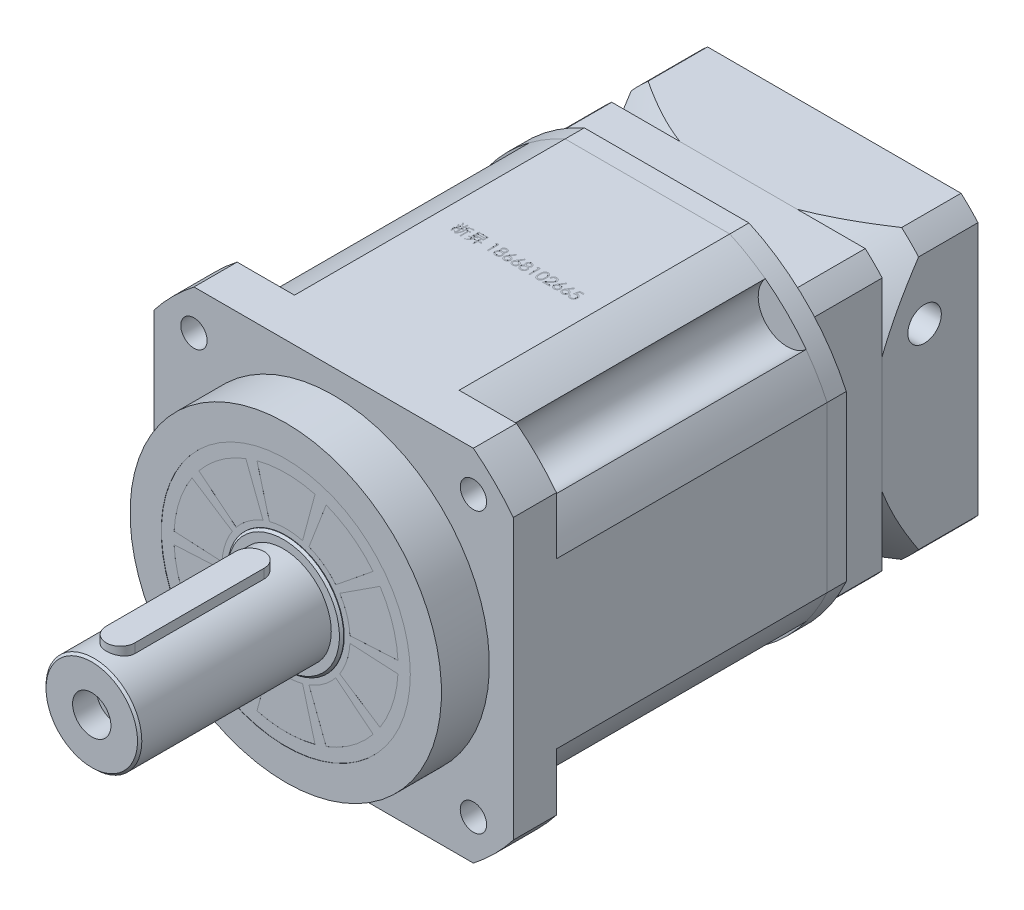
SolidWorks part; units mm, degrees
ref_plane "前视基准面" through (0, 0, 0) normal (0, 0, 1) x (1, 0, 0)
ref_plane "上视基准面" through (0, 0, 0) normal (0, 1, 0) x (1, 0, 0)
ref_plane "右视基准面" through (0, 0, 0) normal (1, 0, 0) x (0, 0, -1)
sketch "草图1" plane through (0, 0, 0) normal (1, 0, 0) x (0, 0, -1)
  line L0 (-155, 0) -> (155, 0) construction
  line L1 (155, 0) -> (155, 75)
  line L2 (155, 75) -> (-54, 75)
  line L3 (-54, 75) -> (-54, 65)
  line L4 (-54, 65) -> (-74, 65)
  line L5 (-74, 65) -> (-74, 24.3)
  line L6 (-74, 24.3) -> (-75, 24.3)
  line L7 (-75, 24.3) -> (-75, 20)
  line L8 (-75, 20) -> (-155, 20)
  line L9 (-155, 20) -> (-155, 0)
  line L10 (155, 55) -> (145, 55)
  line L11 (145, 55) -> (145, 11)
  line L12 (145, 11) -> (95.5, 11)
  line L13 (95.5, 11) -> (95.5, 0)
  line L14 (155, 44) -> (110.375, 44)
  line L15 (110.375, 44) -> (110.375, 0)
  line L16 (132.6875, 44) -> (132.6875, 0) construction
  line L17 (155, 44) -> (145, 11) construction
  line L18 (150, 27.5) -> (110.375, 27.5) construction
  point P3 (-36, 75)
  point P12 (-149, 20)
  point P13 (-83, 20)
  point P14 (95.5, 0)
  point P15 (145, 0)
  point P18 (85, 75)
  point P22 (115, 75)
  point P30 (132.6875, 27.5)
  point P31 (132.6875, -27.5)
  point P32 (-75, 0)
  point P33 (5, 0)
  point P34 (-5, 0)
  point P35 (145, 0)
  point P36 (105, 0)
  point P37 (77, 75)
  dimension "D1" = 150
  dimension "A" = 310
  dimension "D2" = 18
  dimension "D3" = 20
  dimension "D4" = 80
  dimension "D5" = 66
  dimension "D6" = 6
  dimension "D7" = 40
  dimension "D8" = 48.6
  dimension "D9" = 130
  dimension "D10" = 101
  dimension "D11" = 50
  dimension "C" = 59.5
  dimension "D12" = 10
  dimension "D13" = 110
  dimension "D14" = 22
  dimension "D15" = 70
  dimension "D16" = 40
  dimension "D17" = 44.625
  dimension "D18" = 88
  dimension "D19" = 21
  dimension "D20" = 80
  dimension "D21" = 10
  dimension "D22" = 10
  dimension "D23" = 8
sketch "草图2" plane through (0, 0, 0) normal (0, 0, 1) x (1, 0, 0)
  line L0 (0, 0) -> (0, 75) construction
  line L1 (-75, 75) -> (75, 75)
  line L2 (-75, 75) -> (-75, -75)
  line L3 (-75, -75) -> (75, -75)
  line L4 (75, 75) -> (75, -75)
  line L5 (0, 0) -> (75, 0) construction
  line L6 (-6, 23) -> (6, 23)
  line L7 (6, 23) -> (6, 19.0788)
  line L8 (-6, 23) -> (-6, 19.0788)
  line L9 (0, 0) -> (58.3363, 58.3363) construction
  line L10 (0, 0) -> (-51.2652, 51.2652) construction
  line L12 (-60, 60) -> (60, 60)
  line L13 (-60, 60) -> (-60, -60)
  line L14 (-60, -60) -> (60, -60)
  line L15 (60, 60) -> (60, -60)
  circle A0 centre (0, 0) radius 20
  circle A1 centre (0, 0) radius 8
  circle A2 centre (0, 0) radius 82.5 construction
  circle A3 centre (58.3363, 58.3363) radius 5.5
  circle A4 centre (0, 0) radius 95
  circle A5 centre (-51.2652, 51.2652) radius 4
  circle A7 centre (58.3363, 58.3363) radius 12.1
  circle A8 centre (0, 0) radius 72.5 construction
  point P13 (0, -20)
  dimension "D2" = 12
  dimension "D4" = 16
  dimension "D5" = 165
  dimension "D7" = 11
  dimension "D8" = 190
  dimension "D9" = 8
  dimension "D11" = 24.2
  dimension "D12" = 145
  dimension "D1" = 150
  dimension "D3" = 43
  dimension "D6" = 45
  dimension "D10" = 45
  dimension "B" = 120
sketch "草图3" plane through (0, 0, 0) normal (0, 0, 1) x (1, 0, 0)
  line L0 (-75, 75) -> (75, 75) construction
  line L1 (-75, 75) -> (-75, -75) construction
  line L2 (-75, -75) -> (75, -75) construction
  line L3 (75, 75) -> (75, -75) construction
  line L4 (-75, 75) -> (75, 75)
  line L5 (-75, 75) -> (-75, -75)
  line L6 (-75, -75) -> (75, -75)
  line L7 (75, 75) -> (75, -75)
extrude "凸台-拉伸1" add sketch "草图3" along normal up to vertex (54 mm away) from vertex up to point (0, 75, 54) starting at point (0, 75, -85)
sketch "草图33" plane through (0, 0, 0) normal (0, 0, 1) x (1, 0, 0)
  line L0 (-60, 60) -> (-60, -60) construction
  line L1 (-60, -60) -> (60, -60) construction
  line L2 (60, 60) -> (60, -60) construction
  line L3 (-60, 60) -> (60, 60) construction
  line L4 (-60, 60) -> (-60, -60)
  line L5 (-60, -60) -> (60, -60)
  line L6 (60, 60) -> (60, -60)
  line L7 (-60, 60) -> (60, 60)
extrude "凸台-拉伸7" add sketch "草图33" along normal up to vertex (-85 mm away) from vertex up to point (0, 75, -85) starting at point (0, 75, -155)
sketch "草图4" plane through (0, 0, 0) normal (1, 0, 0) x (0, 0, -1)
  line L0 (-54, 65) -> (-74, 65) construction
  line L1 (-54, 65) -> (-74, 65)
  line L2 (-74, 65) -> (-74, 0)
  line L3 (-155, 0) -> (155, 0) construction
  line L4 (-74, 0) -> (-54, 0)
  line L5 (-54, 0) -> (-54, 65)
revolve "旋转1" add sketch "草图4" angle 360 about L4
sketch "草图5" plane through (0, 0, 74) normal (0, 0, 1) x (1, 0, 0)
  circle A0 centre (0, 0) radius 52
  dimension "D1" = 104
extrude "切除-拉伸1" cut sketch "草图5" against normal blind 0.1
sketch "草图6" plane through (0, 0, 0) normal (1, 0, 0) x (0, 0, -1)
  line L0 (-155, 20) -> (-155, 0) construction
  line L1 (-75, 20) -> (-155, 20) construction
  line L2 (-75, 24.3) -> (-75, 20) construction
  line L3 (-155, 20) -> (-155, 0)
  line L4 (-75, 20) -> (-155, 20)
  line L5 (-75, 24.3) -> (-75, 20)
  line L6 (-75, 24.3) -> (-54, 24.3)
  line L7 (-54, -75) -> (-54, 75) construction
  line L8 (-155, 0) -> (-54, 0)
  line L9 (-155, 0) -> (155, 0) construction
  line L10 (-54, 0) -> (-54, 24.3)
revolve "旋转2" add sketch "草图6" angle 360 about L8
sketch "草图13" plane through (0, 0, 155) normal (0, 0, 1) x (1, 0, 0)
  circle A0 centre (0, 0) radius 8 construction
  circle A1 centre (0, 0) radius 8
extrude "切除-拉伸7" cut sketch "草图13" against normal blind 10
cosmetic thread "装饰螺纹线1" parameters "D2"=16.1
sketch "草图8" plane through (0, 0, 0) normal (0, 1, 0) x (1, 0, 0)
  line L1 (-6, -89) -> (6, -89) construction
  line L2 (-6, -89) -> (-6, -143)
  line L3 (-6, -143) -> (6, -143) construction
  line L4 (6, -89) -> (6, -143)
  arc A0 (6, -89) -> (-6, -89) centre (0, -89) ccw
  arc A1 (-6, -143) -> (6, -143) centre (0, -143) ccw
  point P5 (0, -83)
  point P7 (0, -149)
extrude "凸台-拉伸2" add sketch "草图8" against normal up to vertex (-19.0788 mm away) from vertex up to point (6, 19.0788, 0) starting at point (6, 23, 0)
chamfer "倒角1" distance 0.9 angle 45 2 edges at (24.3, 0, 75) (20, 0, 155)
sketch "草图7" plane through (0, 0, 73.9) normal (0, 0, 1) x (1, 0, 0)
  line L0 (-6.9182, 25.8192) -> (-12.1127, 45.2053)
  line L1 (6.9182, 25.8192) -> (12.1127, 45.2053)
  line L2 (0, 20) -> (0, 0) construction
  arc A0 (12.1127, 45.2053) -> (-12.1127, 45.2053) centre (0, 0) ccw
  arc A1 (6.9182, 25.8192) -> (-6.9182, 25.8192) centre (0, 0) ccw
  dimension "D1" = 53.46
  dimension "D2" = 93.6
  dimension "D3" = 30
  dimension "D4" = 15
extrude "切除-拉伸2" cut sketch "草图7" against normal blind 0.01
pattern_circular "阵列(圆周)1" count 10 over 360 about axis through (0, 0, 74) along (0, 0, 1) of "切除-拉伸2"
sketch "草图9" plane through (0, 0, 0) normal (0, 0, 1) x (1, 0, 0)
  circle A1 centre (0, 0) radius 82.5 construction
  circle A2 centre (0, 0) radius 82.5
extrude "切除-拉伸3" cut sketch "草图9" along normal up to vertex (36 mm away) from vertex flip side to cut up to point (0, 75, 36) starting at point (0, 75, -115)
sketch "草图10" plane through (0, 0, 0) normal (0, 0, 1) x (1, 0, 0)
  circle A0 centre (58.3363, 58.3363) radius 12.1 construction
  circle A1 centre (58.3363, 58.3363) radius 12.1
extrude "切除-拉伸4" cut sketch "草图10" along normal up to vertex (36 mm away) from vertex up to point (0, 75, 36) starting at point (0, 75, -77)
sketch "草图11" plane through (0, 0, 0) normal (0, 0, 1) x (1, 0, 0)
  circle A0 centre (58.3363, 58.3363) radius 5.5 construction
  circle A1 centre (58.3363, 58.3363) radius 5.5
extrude "切除-拉伸5" cut sketch "草图11" along normal up to vertex (54 mm away) from vertex up to point (0, 75, 54) starting at point (0, 75, 36)
pattern_circular "阵列(圆周)2" count 4 over 360 about axis through (0, 0, 74) along (0, 0, 1) of "切除-拉伸4", "切除-拉伸5"
sketch "草图12" plane through (0, 0, 0) normal (0, 0, 1) x (1, 0, 0)
  circle A0 centre (0, 0) radius 95 construction
  circle A1 centre (0, 0) radius 95
extrude "切除-拉伸6" cut sketch "草图12" along normal up to vertex (54 mm away) from vertex flip side to cut up to point (0, 75, 54) starting at point (0, 75, -85)
sketch "草图34" plane through (0, 0, 0) normal (0, 0, 1) x (1, 0, 0)
  circle A0 centre (0, 0) radius 80
  dimension "D1" = 160
extrude "切除-拉伸13" cut sketch "草图34" along normal up to vertex (-85 mm away) from vertex flip side to cut up to point (0, 75, -85) starting at point (-60, 60, -155)
sketch "草图14" plane through (0, 0, -155) normal (0, 0, -1) x (-1, 0, 0)
  circle A0 centre (51.2652, 51.2652) radius 4 construction
  circle A1 centre (51.2652, 51.2652) radius 4
extrude "切除-拉伸8" cut sketch "草图14" against normal blind 10
cosmetic thread "装饰螺纹线2" parameters "D2"=8.1
pattern_circular "阵列(圆周)3" count 4 over 360 about axis through (0, 0, 74) along (0, 0, 1) of "切除-拉伸8"
sketch "草图15" plane through (0, 0, 0) normal (1, 0, 0) x (0, 0, -1)
  line L4 (155, 55) -> (110.375, 55)
  line L5 (110.375, 55) -> (110.375, 0)
  line L6 (110.375, 0) -> (155, 0)
  line L9 (155, 0) -> (155, 55)
revolve "切除-旋转1" cut sketch "草图15" angle 360 about L6
sketch "草图17" plane through (0, 0, -110.375) normal (0, 0, -1) x (-1, 0, 0)
  line L0 (0, 39.5505) -> (0, -39.6) construction
  line L1 (-1.98, 39.5505) -> (-1.98, -39.5505)
  line L2 (1.98, 39.5505) -> (1.98, -39.5505)
  line L3 (-28.494, 27.5) -> (28.494, 27.5) construction
  arc A0 (-1.98, 39.5505) -> (-1.98, -39.5505) centre (0, 0) ccw
  arc A1 (1.98, -39.5505) -> (1.98, 39.5505) centre (0, 0) ccw
  dimension "D1" = 79.2
  dimension "D2" = 3.96
extrude "凸台-拉伸3" add sketch "草图17" along normal up to vertex (34.625 mm away) up to point (0, 0, -145)
sketch "草图19" plane through (0, 0, 0) normal (1, 0, 0) x (0, 0, -1)
  line L0 (95.5, 11) -> (95.5, 0) construction
  line L1 (95.5, 11) -> (95.5, 0)
  line L2 (95.5, 11) -> (155, 11)
  line L3 (155, 0) -> (155, 75) construction
  line L4 (155, 11) -> (155, 0)
  line L5 (155, 0) -> (95.5, 0)
revolve "切除-旋转3" cut sketch "草图19" angle 360 about L5
sketch "草图26" plane through (0, 0, 0) normal (1, 0, 0) x (0, 0, -1)
  line L0 (145, 44) -> (145, 55)
  line L1 (145, 55) -> (145, 11) construction
  line L2 (155, 44) -> (110.375, 44) construction
  line L3 (145, 55) -> (110.375, 55)
  line L4 (110.375, 55) -> (110.375, 44)
  line L5 (110.375, 44) -> (145, 44)
  line L6 (-155, 0) -> (155, 0) construction
  line L7 (-155, 0) -> (155, 0) construction
revolve "旋转3" add sketch "草图26" angle 360 about L7
sketch "草图20" plane through (0, 0, 0) normal (1, 0, 0) x (0, 0, -1)
  circle A0 centre (132.6875, 27.5) radius 7
  dimension "D1" = 14
extrude "切除-拉伸9" cut sketch "草图20" against normal blind 10 and the other way through all from vertex starting at point (28.494, 27.5, -110.375)
sketch "草图25" plane through (0, 0, 0) normal (1, 0, 0) x (0, 0, -1)
  circle A0 centre (132.6875, -27.5) radius 7
  circle A1 centre (132.6875, 27.5) radius 7 construction
extrude "切除-拉伸11" cut sketch "草图25" against normal through all and the other way blind 10 from vertex starting at point (-28.494, 27.5, -110.375)
sketch "螺钉草图1" plane through (18.494, 15.4199, -49.0441) normal (1, 0, 0) x (0, 0, -1)
  circle A0 centre (83.6434, 12.0801) radius 6.65
  dimension "D1" = 13.3
extrude "拉伸-螺钉(内六角)" add sketch "螺钉草图1" along normal blind 7.98
fillet "圆角-螺钉(内六角)" radius 0.4433 1 edges at (26.474, 27.5, -139.3375)
sketch "螺钉草图2" plane through (26.474, 13.5, -50.375) normal (1, 0, 0) x (0, 0, -1)
  line L1 (86.9198, 14) -> (84.6161, 17.99)
  line L2 (84.6161, 17.99) -> (80.0089, 17.99)
  line L3 (80.0089, 17.99) -> (77.7052, 14)
  line L4 (77.7052, 14) -> (80.0089, 10.01)
  line L5 (80.0089, 10.01) -> (84.6161, 10.01)
  line L6 (84.6161, 10.01) -> (86.9198, 14)
  circle A0 centre (82.3125, 14) radius 3.99 construction
  dimension "D1" = 7.98
extrude "切除-螺钉(内六角)" cut sketch "螺钉草图2" against normal blind 4.655
sketch "草图23" plane through (0, 0, 0) normal (1, 0, 0) x (0, 0, -1)
  circle A0 centre (132.6875, 27.5) radius 4.9
  dimension "D1" = 9.8
extrude "凸台-拉伸5" add sketch "草图23" along normal mid plane 3.96
pattern_circular "阵列(圆周)4" count 2 over 360 about axis through (0, 0, 74) along (0, 0, 1) of "拉伸-螺钉(内六角)", "圆角-螺钉(内六角)", "切除-螺钉(内六角)", "凸台-拉伸5"
sketch "草图27" plane through (0, 0, 0) normal (1, 0, 0) x (0, 0, -1)
  line L0 (115, 64.8) -> (115, 164.8)
  line L1 (115, 164.8) -> (215, 164.8)
  line L2 (215, 164.8) -> (115, 64.8)
  line L3 (-155, 0) -> (155, 0) construction
  line L4 (-155, 0) -> (155, 0) construction
  dimension "D1" = 100
  dimension "D2" = 45
  dimension "D3" = 129.6
revolve "切除-旋转4" cut sketch "草图27" angle 360 about L4
sketch "草图28" plane through (0, 0, 0) normal (1, 0, 0) x (0, 0, -1)
  line L0 (77, 75) -> (77, -75)
  line L2 (85, -75) -> (-36, -75) construction
split line "分割线1"
sketch "草图35" plane through (0, 0, 0) normal (1, 0, 0) x (0, 0, -1)
  line L0 (115, 75) -> (115, -60)
split line "分割线2"
sketch "孔输出草图1" plane through (0, 0, 0) normal (0, 0, 1) x (1, 0, 0)
  line L0 (0, 0) -> (0, 20) construction
  line L1 (-6, 23.3) -> (6, 23.3)
  line L2 (6, 23.3) -> (6, 19.0788)
  line L3 (-6, 23.3) -> (-6, 19.0788)
  circle A0 centre (0, 0) radius 20
  circle A1 centre (0, 0) radius 29.125
  point P7 (0, -20)
  dimension "D1" = 40
  dimension "D4" = 58.25
  dimension "D2" = 12
  dimension "D3" = 43.3
sketch "草图30" [suppressed] plane through (0, 0, 0) normal (0, 0, 1) x (1, 0, 0)
  circle A0 centre (0, 0) radius 29.125 construction
  circle A1 centre (0, 0) radius 29.125
extrude "凸台-拉伸6" [suppressed] add sketch "草图30" along normal up to vertex
sketch "草图31" [suppressed] plane through (0, 0, 75) normal (0, 0, 1) x (1, 0, 0)
  line L0 (-6, 23.3) -> (-6, 19.0788) construction
  line L1 (-6, 23.3) -> (6, 23.3) construction
  line L2 (6, 23.3) -> (6, 19.0788) construction
  line L3 (-6, 23.3) -> (-6, 19.0788)
  line L4 (-6, 23.3) -> (6, 23.3)
  line L5 (6, 23.3) -> (6, 19.0788)
  circle A0 centre (0, 0) radius 20 construction
  arc A1 (-6, 19.0788) -> (6, 19.0788) centre (0, 0) ccw
extrude "切除-拉伸12" [suppressed] cut sketch "草图31" against normal up to vertex
chamfer "倒角2" [suppressed] distance 1.0825 angle 45
sketch "草图32" [suppressed] plane through (0, 0, 0) normal (1, 0, 0) x (0, 0, -1)
  line L0 (-5, 0) -> (-5, 14)
  line L1 (-5, 14) -> (5, 14)
  line L2 (5, 14) -> (5, 0)
  line L3 (5, 0) -> (-5, 0)
  line L4 (-155, 0) -> (155, 0) construction
  line L5 (-155, 0) -> (155, 0) construction
  dimension "D1" = 28
revolve "切除-旋转5" [suppressed] cut sketch "草图32" angle 360 about L5
sketch "草图36" plane through (0, 0, -95.5) normal (0, 0, -1) x (-1, 0, 0)
  circle A0 centre (0, 0) radius 11.5
  dimension "D1" = 23
extrude "切除-拉伸14" cut sketch "草图36" along normal blind 10
sketch "草图37" plane through (0, 75, 0) normal (0, 1, 0) x (1, 0, 0)
  line L0 (-34.3693, 20.5) -> (34.3693, 20.5) construction
  line L1 (-34.3693, 77) -> (-34.3693, -36) construction
  line L2 (34.3693, -36) -> (34.3693, 77) construction
  text T0 "浙昇 18668102665" font "Century Gothic" height 4.5
extrude "LOGO" cut sketch "草图37" against normal blind 0.01
